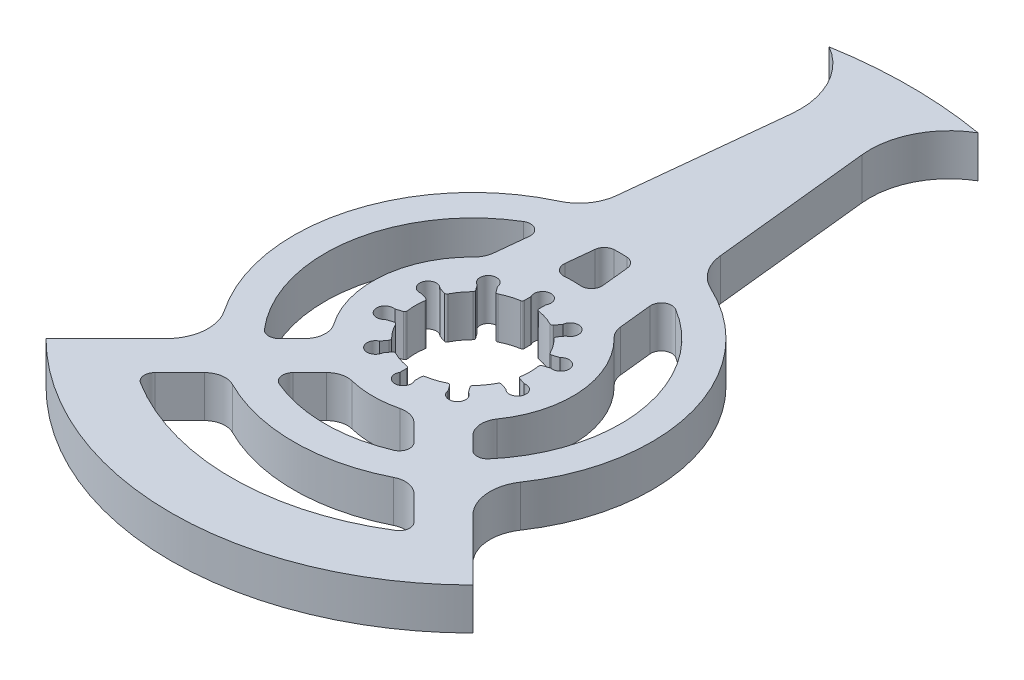
SolidWorks part; units mm, degrees
material "AISI Type A2 Tool Steel"
ref_plane "Front Plane" through (0, 0, 0) normal (0, 0, 1) x (1, 0, 0)
ref_plane "Top Plane" through (0, 0, 0) normal (0, 1, 0) x (1, 0, 0)
ref_plane "Right Plane" through (0, 0, 0) normal (1, 0, 0) x (0, 0, -1)
other "Center of Mass"
other "Bounding Box"
ref_plane "Default Plane" through (0, 2.286, 19.05) normal (0, -1, 0) x (-1, 0, 0)
sketch "Sketch1" plane through (0, 0, 0) normal (0, 1, 0) x (1, 0, 0)
  circle A0 centre (0, 0) radius 133.35 construction
  circle A1 centre (0, 0) radius 30.48
  circle A2 centre (0, 0) radius 17.4625
  dimension "D1" = 266.7
  dimension "D2" = 60.96
  dimension "D3" = 34.925
extrude "Boss-Extrude1" add sketch "Sketch1" along normal mid plane 12.7
sketch "Sketch2" plane through (0, 6.35, 0) normal (0, 1, 0) x (1, 0, 0)
  line L0 (-10.795, 107.95) -> (-19.6961, 23.2614)
  line L1 (19.6961, 23.2614) -> (10.795, 107.95)
  line L4 (0, 0) -> (0, 133.35) construction
  line L5 (-10.795, 107.95) -> (0, 107.95) construction
  line L6 (0, 107.95) -> (10.795, 107.95) construction
  line L7 (-22.6939, 131.4048) -> (0, 0) construction
  line L8 (-22.6939, 131.4048) -> (125.4677, 45.1673) construction
  circle A0 centre (0, 0) radius 133.35 construction
  circle A1 centre (0, 0) radius 133.35 construction
  arc A2 (-22.6939, 131.4048) -> (22.6939, 131.4048) centre (0, 0) cw
  arc A3 (-22.6939, 131.4048) -> (-10.795, 107.95) centre (-34.8727, 110.4807) cw
  circle A5 centre (0, 0) radius 30.48
  arc A6 (19.6961, 23.2614) -> (-19.6961, 23.2614) centre (0, 0) ccw
  arc A7 (-19.6961, 23.2614) -> (19.6961, 23.2614) centre (0, 0) ccw construction
  arc A8 (10.795, 107.95) -> (22.6939, 131.4048) centre (34.8727, 110.4807) cw
  dimension "D4" = 25.4
  dimension "D5" = 6
  dimension "D6" = 10.795
  dimension "D1" = 50
  dimension "D2" = 0
extrude "Boss-Extrude2" add sketch "Sketch2" against normal through all
sketch "Sketch3" plane through (0, 6.35, 0) normal (0, 1, 0) x (1, 0, 0)
  line L0 (-65.1069, -65.1069) -> (-21.5526, -21.5526)
  line L1 (21.5526, -21.5526) -> (65.1069, -65.1069)
  line L2 (0, -30.48) -> (0, -92.075) construction
  line L4 (-21.5526, -21.5526) -> (0, 0) construction
  line L5 (0, 0) -> (21.5526, -21.5526) construction
  arc A0 (-65.1069, -65.1069) -> (65.1069, -65.1069) centre (0, 0) ccw
  circle A1 centre (0, 0) radius 30.48 construction
  arc A3 (-21.5526, -21.5526) -> (21.5526, -21.5526) centre (0, 0) ccw
  point P13 (0, -92.075)
  dimension "D2" = 92.075
  dimension "D1" = 90
extrude "Boss-Extrude3" add sketch "Sketch3" against normal through all
sketch "Sketch5" plane through (0, 6.35, 0) normal (0, 1, 0) x (1, 0, 0)
  line L0 (0, 17.4625) -> (0, 21.2725) construction
  line L2 (-2.2225, 17.3205) -> (2.2225, 17.3205)
  line L3 (-2.2225, 17.3205) -> (-2.2225, 20.0168)
  line L5 (2.2225, 17.3205) -> (2.2225, 20.0168)
  arc A0 (2.2225, 20.0168) -> (-2.2225, 20.0168) centre (0, 21.2725) ccw
  circle A1 centre (0, 0) radius 17.4625 construction
  circle A2 centre (0, 21.2725) radius 4.5847 construction
  dimension "D2" = 5.1054
  dimension "D4" = 9.1694
  dimension "D1" = 3.81
  dimension "D3" = 4.445
extrude "Cut-Extrude2" cut sketch "Sketch5" against normal through all
pattern_circular "CirPattern1" count 10 over 360 about axis through (0, 6.35, 0) along (0, -1, 0) of "Cut-Extrude2"
sketch "Sketch6" plane through (0, 6.35, 0) normal (0, 1, 0) x (1, 0, 0)
  circle A0 centre (0, 0) radius 17.526
  arc A1 (-11.9788, 12.7062) -> (-15.786, 7.466) centre (0, 0) ccw construction
  dimension "D1" = 0.0635
extrude "Cut-Extrude3" cut sketch "Sketch6" against normal through all
sketch "Sketch7" plane through (0, 6.35, 0) normal (0, 1, 0) x (1, 0, 0)
  line L0 (-42.2705, -60.231) -> (-10.6123, -28.5729)
  line L1 (10.6123, -28.5729) -> (42.2705, -60.231)
  line L3 (-21.5526, -21.5526) -> (-65.1069, -65.1069) construction
  line L4 (65.1069, -65.1069) -> (21.5526, -21.5526) construction
  line L5 (-42.2705, -60.231) -> (-51.2508, -51.2508) construction
  line L6 (42.2705, -60.231) -> (51.2508, -51.2508) construction
  arc A0 (-10.6123, -28.5729) -> (10.6123, -28.5729) centre (0, 0) ccw
  arc A1 (-42.2705, -60.231) -> (42.2705, -60.231) centre (0, 0) ccw
  arc A2 (-65.1069, -65.1069) -> (65.1069, -65.1069) centre (0, 0) ccw construction
  arc A4 (21.5526, -21.5526) -> (19.6961, 23.2614) centre (0, 0) ccw construction
  dimension "D1" = 18.4912
  dimension "D2" = 12.7
extrude "Cut-Extrude4" cut sketch "Sketch7" against normal through all
sketch "Sketch8" plane through (0, 6.35, 0) normal (0, 1, 0) x (1, 0, 0)
  circle A0 centre (0, 0) radius 45.085
  circle A1 centre (0, 0) radius 54.61
  dimension "D1" = 9.525
  dimension "D2" = 109.22
extrude "Boss-Extrude4" add sketch "Sketch8" against normal through all
sketch "Sketch11" plane through (0, 6.35, 0) normal (0, 1, 0) x (1, 0, 0)
  line L0 (-6.2352, 29.8354) -> (-4.6578, 44.8438)
  line L1 (4.6578, 44.8438) -> (6.2352, 29.8354)
  line L3 (-17.7867, 41.4281) -> (-19.6961, 23.2614) construction
  line L4 (19.6961, 23.2614) -> (17.7867, 41.4281) construction
  line L5 (-5.4465, 37.3396) -> (-18.0769, 38.6671) construction
  line L6 (5.4465, 37.3396) -> (18.0769, 38.6671) construction
  arc A0 (-6.2352, 29.8354) -> (6.2352, 29.8354) centre (0, 0) cw
  arc A1 (-4.6578, 44.8438) -> (4.6578, 44.8438) centre (0, 0) cw
  arc A2 (-19.6961, 23.2614) -> (-21.5526, -21.5526) centre (0, 0) ccw construction
  arc A3 (-17.7867, 41.4281) -> (-31.8799, -31.8799) centre (0, 0) ccw construction
  dimension "D1" = 12.7
extrude "Cut-Extrude6" cut sketch "Sketch11" against normal through all
fillet "Fillet1" radius 6.35 8 edges at (-21.5526, 0, 21.5526) (21.5526, 0, 21.5526) (19.6961, 0, -23.2614) (-19.6961, 0, -23.2614) (10.6123, 0, 28.5729) (-10.6123, 0, 28.5729) (28.5761, 0, 46.5366) (-28.5761, 0, 46.5366)
fillet "Fillet6" radius 0.635 20 edges at (-12.0164, 0, -12.758) (-15.8469, 0, -7.4858) (-17.2204, 0, -3.2584) (-17.2204, 0, 3.2584) (-15.8469, 0, 7.4858) (-12.0164, 0, 12.758) (-8.4203, 0, 15.3707) (-2.2225, 0, 17.3845) (2.2225, 0, 17.3845) (8.4203, 0, 15.3707) (12.0164, 0, 12.758) (15.8469, 0, 7.4858) (17.2204, 0, 3.2584) (17.2204, 0, -3.2584) (15.8469, 0, -7.4858) (12.0164, 0, -12.758) (8.4203, 0, -15.3707) (2.2225, 0, -17.3845) (-2.2225, 0, -17.3845) (-8.4203, 0, -15.3707)
fillet "Fillet7" radius 3.175 12 edges at (-21.6087, 0, 39.5692) (21.6087, 0, 39.5692) (31.8799, 0, 31.8799) (-31.8799, 0, 31.8799) (-17.7867, 0, -41.4281) (17.7867, 0, -41.4281) (42.2705, 0, 60.231) (-42.2705, 0, 60.231) (-6.2352, 0, -29.8354) (6.2352, 0, -29.8354) (4.6578, 0, -44.8438) (-4.6578, 0, -44.8438)
fillet "Fillet8" radius 12.7 4 edges at (-16.6754, 0, -52.0018) (16.6754, 0, -52.0018) (38.6151, 0, 38.6151) (-38.6151, 0, 38.6151)
equation "\"Unit Measure\"= \"BoundingVolume\" / \"Thickness\"'in^2"
